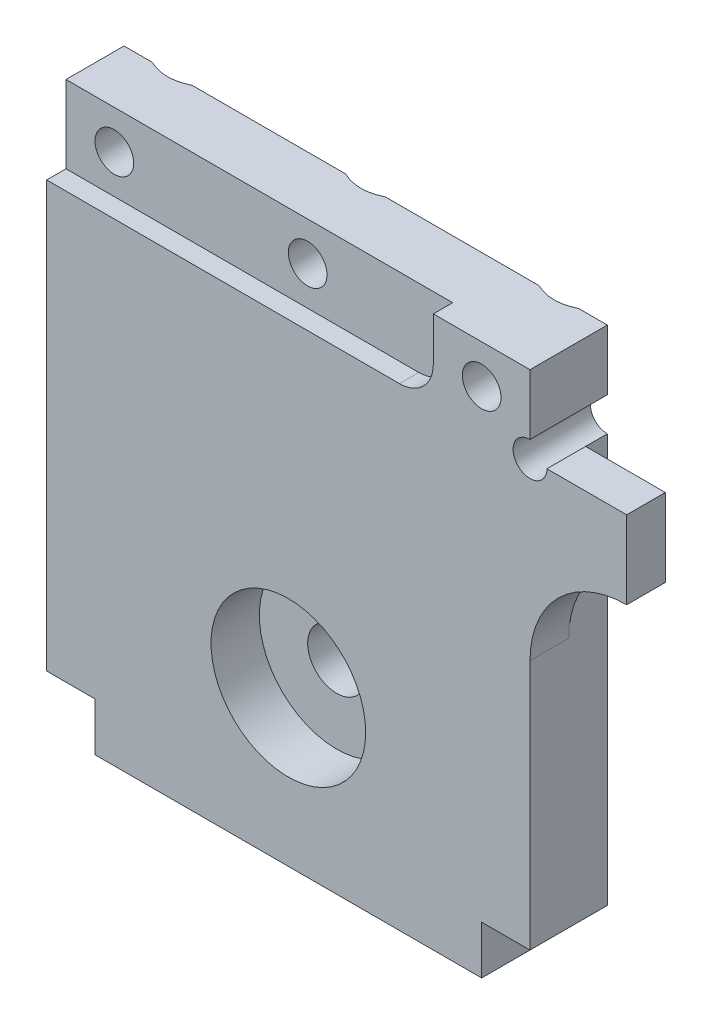
SolidWorks part; units mm, degrees
material "PVC rigide"
ref_plane "Plan de face" through (0, 0, 0) normal (0, 0, 1) x (1, 0, 0)
ref_plane "Plan de dessus" through (0, 0, 0) normal (0, 1, 0) x (1, 0, 0)
ref_plane "Plan de droite" through (0, 0, 0) normal (1, 0, 0) x (0, 0, -1)
sketch "Esquisse1" plane through (0, 0, 0) normal (0, 0, 1) x (1, 0, 0)
  line L0 (-25, -23.5) -> (-20, -23.5)
  line L1 (-25, 28.5) -> (25, 28.5)
  line L2 (-25, 28.5) -> (-25, -23.5)
  line L3 (-20, -28.5) -> (20, -28.5)
  line L4 (25, 28.5) -> (25, -23.5)
  line L5 (-20, -23.5) -> (-20, -28.5)
  line L6 (25, -23.5) -> (20, -23.5)
  line L7 (20, -23.5) -> (20, -28.5)
  line L8 (25, -28.5) -> (25, -23.5) construction
  line L9 (25, -28.5) -> (20, -28.5) construction
  line L10 (-25, -23.5) -> (-25, -28.5) construction
  line L11 (-25, -28.5) -> (-20, -28.5) construction
  line L12 (25, 28.5) -> (-25, -28.5) construction
  line L13 (-25, 28.5) -> (25, -28.5) construction
  point P9 (0, 0)
  point P12 (25, 28.2413)
  dimension "D4" = 5
  dimension "D1" = 50
  dimension "D2" = 57
  dimension "D3" = 5
extrude "Boss.-Extru.1" add sketch "Esquisse1" along normal blind 8
sketch "Esquisse2" plane through (0, -28.5, 0) normal (0, -1, 0) x (1, 0, 0)
  line L0 (-25, 4) -> (25, 4) construction
  line L1 (-25, 8) -> (-25, 0) construction
  line L2 (25, 8) -> (25, 0) construction
  circle A0 centre (-15, 4) radius 2
  circle A1 centre (15, 4) radius 2
  dimension "D1" = 4
  dimension "D2" = 10
  dimension "D3" = 10
extrude "Enlèv. mat.-Extru.1" cut sketch "Esquisse2" against normal blind 10
sketch "Esquisse3" plane through (0, 0, 8) normal (0, 0, 1) x (1, 0, 0)
  line L0 (-25.973, 24.5) -> (39.229, 24.5) construction
  line L1 (25, 28.5) -> (-25, 28.5) construction
  line L2 (-25, 28.5) -> (-25, -23.5) construction
  line L3 (25, -23.5) -> (25, 28.5) construction
  circle A0 centre (-20, 24.5) radius 2
  circle A1 centre (20, 24.5) radius 2
  circle A2 centre (0, 24.5) radius 2
  dimension "D2" = 4
  dimension "D1" = 4
  dimension "D3" = 5
  dimension "D4" = 5
extrude "Enlèv. mat.-Extru.2" cut sketch "Esquisse3" against normal through all
chamfer "Chanfrein1" distance 2.5 angle 45 3 edges at (22, 24.5, 0) (-18, 24.5, 0) (2, 24.5, 0)
sketch "Esquisse4" plane through (0, 0, 8) normal (0, 0, 1) x (1, 0, 0)
  line L0 (-32.372, -12.5) -> (112.9613, -12.5) construction
  line L1 (0, -17.2825) -> (0, 28.5) construction
  line L3 (-20, -28.5) -> (20, -28.5) construction
  line L4 (25, 28.5) -> (-25, 28.5) construction
  circle A0 centre (0, -12.5) radius 8
  point P17 (0, -12.5)
  dimension "D1" = 16
  dimension "D2" = 16
extrude "Enlèv. mat.-Extru.3" cut sketch "Esquisse4" against normal blind 5
sketch "Esquisse5" plane through (0, 0, 3) normal (0, 0, 1) x (1, 0, 0)
  circle A0 centre (0, -12.5) radius 3
  circle A1 centre (0, -12.5) radius 8 construction
  dimension "D1" = 6
extrude "Enlèv. mat.-Extru.4" cut sketch "Esquisse5" against normal through all
sketch "Esquisse6" plane through (0, 0, 8) normal (0, 0, 1) x (1, 0, 0)
  line L1 (-25, 28.5) -> (15, 28.5)
  line L2 (-25, 28.5) -> (-25, 20.5)
  line L3 (-25, 20.5) -> (15, 20.5)
  line L5 (15, 20.5) -> (15, 28.5)
  circle A0 centre (-20, 24.5) radius 2 construction
  dimension "D1" = 4
extrude "Enlèv. mat.-Extru.5" cut sketch "Esquisse6" against normal blind 2
fillet "Congé1" radius 3.5 1 edges at (15, 20.5, 7)
sketch "Esquisse9" plane through (0, 0, 8) normal (0, 0, 1) x (1, 0, 0)
  line L0 (25, 2.436) -> (25, 20.5)
  line L1 (25, -23.5) -> (25, 28.5) construction
  line L2 (35, 12.436) -> (35, 20.5)
  line L3 (35, 20.5) -> (25, 20.5)
  line L4 (-25, 20.5) -> (11.5, 20.5) construction
  arc A0 (35, 12.436) -> (25, 2.436) centre (35, 2.436) ccw
  point P8 (0, 0)
  dimension "D2" = 10
  dimension "D1" = 10
extrude "Boss.-Extru.2" add sketch "Esquisse9" against normal blind 4
sketch "Esquisse10" plane through (0, 0, 8) normal (0, 0, 1) x (1, 0, 0)
  circle A0 centre (25, 20.5) radius 1.75
  dimension "D1" = 3.5
extrude "Enlèv. mat.-Extru.8" cut sketch "Esquisse10" against normal blind 8
